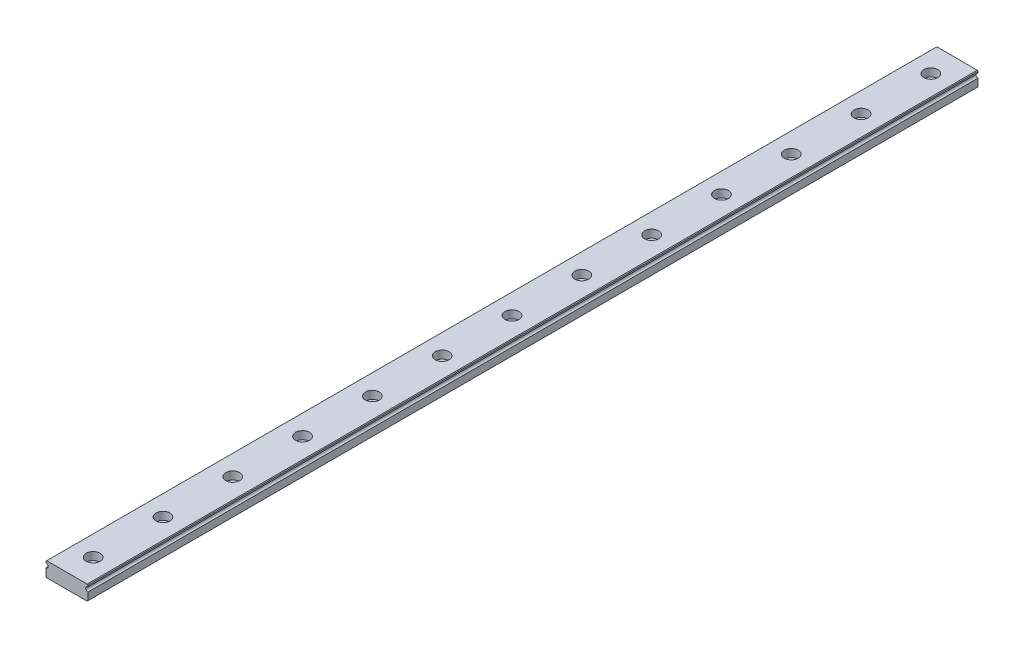
SolidWorks part; units mm, degrees
material "45#"
ref_plane "前视" through (0, 0, 0) normal (0, 0, 1) x (1, 0, 0)
ref_plane "上视" through (0, 0, 0) normal (0, 1, 0) x (1, 0, 0)
ref_plane "右视" through (0, 0, 0) normal (1, 0, 0) x (0, 0, -1)
sketch "草图1" plane through (0, 0, 0) normal (0, 0, 1) x (1, 0, 0)
  line L0 (0, 4.25) -> (0, -4.25) construction
  line L1 (-12, 3) -> (-12, 3.85)
  line L2 (-11.6, 4.25) -> (-12, 3.85)
  line L3 (11.6, 4.25) -> (-11.6, 4.25)
  line L4 (12, 3.85) -> (11.6, 4.25)
  line L5 (12, 3.85) -> (12, 3)
  line L6 (11.6, -4.25) -> (12, -3.85)
  line L7 (11.6, -4.25) -> (6.3, -4.25)
  line L8 (5.7, -4.25) -> (-11.6, -4.25)
  line L9 (-12, -3.85) -> (-11.6, -4.25)
  line L10 (-12, -3.85) -> (-12, 0.5)
  line L11 (12, 0.5) -> (12, -3.85)
  arc A0 (-12, 0.5) -> (-12, 3) centre (-12, 1.75) ccw
  arc A1 (12, 3) -> (12, 0.5) centre (12, 1.75) ccw
  arc A2 (6.3, -4.25) -> (5.7, -4.25) centre (6, -4.25) ccw
extrude "凸台-拉伸1" add sketch "草图1" against normal blind 510
hole_wizard "打孔尺寸根据内六角圆柱头螺钉的类型1" positions "草图3" profile "草图2" counterbore size "M4" standard "Gb" end condition through all
sketch "草图3" plane through (0, 4.25, 0) normal (0, 1, 0) x (1, 0, 0)
  line L0 (0, 510) -> (0, 0) construction
  line L1 (11.6, 510) -> (-11.6, 510) construction
  line L2 (11.6, 0) -> (-11.6, 0) construction
  point P0 (0, 15)
  dimension "D1" = 15
sketch "草图2" plane through (0, 4.25, -15) normal (1, 0, 0) x (0, 0, 1)
  line L0 (0, 0) -> (0, 8.5)
  line L1 (0, 8.5) -> (2.25, 8.5)
  line L3 (2.25, 8.5) -> (2.25, 4.5)
  line L4 (2.25, 4.5) -> (4, 4.5)
  line L5 (4, 4.5) -> (4, 0)
  line L7 (4, 0) -> (0, 0)
  line L11 (0, -6.35) -> (0, 107.95) construction
  dimension "通孔孔直径" = 4.5
  dimension "通孔孔深度" = 8.5
  dimension "柱形沉头孔直径" = 8
  dimension "柱形沉头孔深度" = 4.5
pattern_linear "阵列(线性)1" count 13 spacing 40 along (0, 0, -1) of "打孔尺寸根据内六角圆柱头螺钉的类型1"
